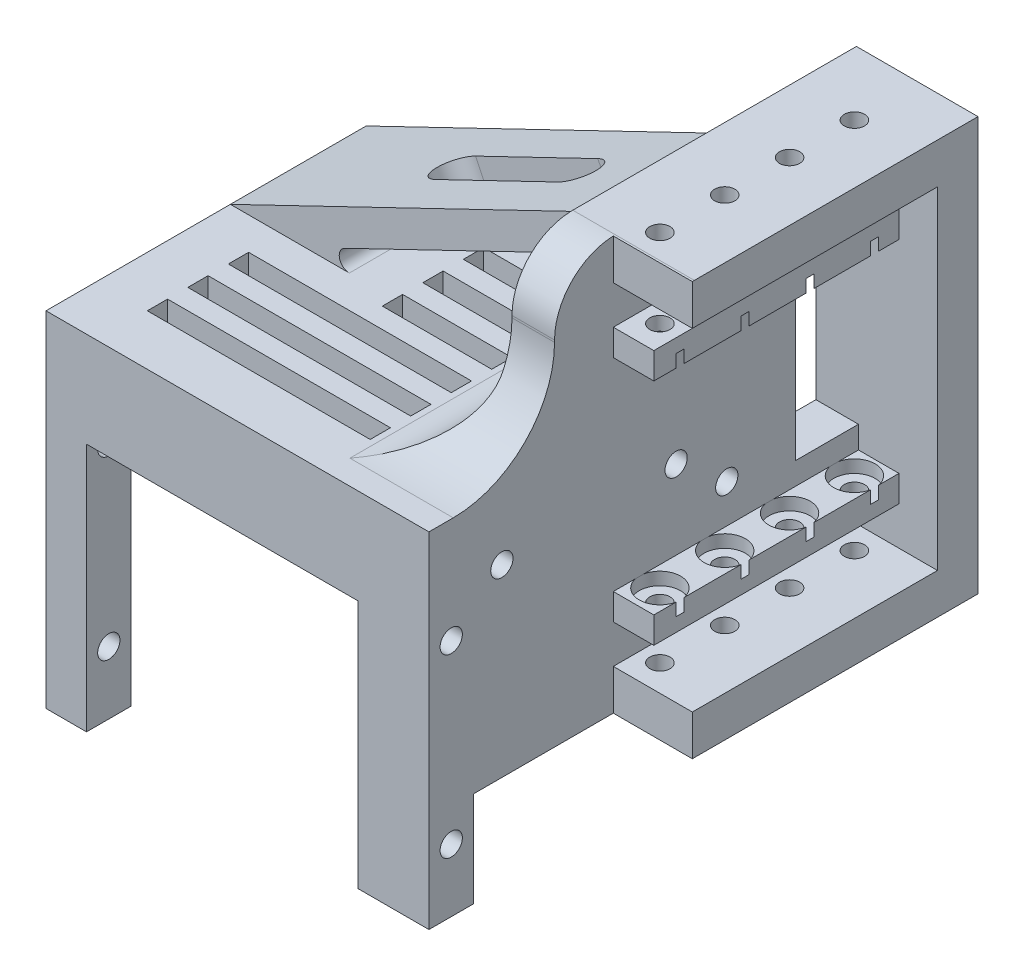
SolidWorks part; units mm, degrees
ref_plane "Front Plane" through (0, 0, 0) normal (0, 0, 1) x (1, 0, 0)
ref_plane "Top Plane" through (0, 0, 0) normal (0, 1, 0) x (1, 0, 0)
ref_plane "Right Plane" through (0, 0, 0) normal (1, 0, 0) x (0, 0, -1)
sketch "Sketch1" plane through (0, 0, 0) normal (0, 0, 1) x (1, 0, 0)
  line L1 (0, 0) -> (57.912, 0)
  line L2 (0, 0) -> (0, 63.754)
  line L3 (0, 63.754) -> (57.912, 63.754)
  line L4 (57.912, 0) -> (57.912, 63.754)
  dimension "D1" = 57.912
  dimension "D2" = 63.754
extrude "Boss-Extrude1" add sketch "Sketch1" against normal blind 58.928
sketch "Sketch3" plane through (0, 0, 0) normal (0, 0, 1) x (1, 0, 0)
  line L0 (42.672, 63.754) -> (0, 43.18)
  line L1 (42.672, 59.2423) -> (14.3644, 45.594)
  line L2 (14.9159, 43.18) -> (42.672, 43.18)
  line L3 (44.437, 60.0933) -> (1.765, 39.5193) construction
  line L4 (0, 63.754) -> (0, 0)
  line L5 (0, 0) -> (57.912, 0)
  line L6 (57.912, 0) -> (57.912, 63.754)
  line L7 (57.912, 63.754) -> (0, 63.754)
  line L8 (0, 63.754) -> (0, 43.18)
  line L9 (5.08, 0) -> (5.08, 31.242)
  line L10 (0, 0) -> (57.912, 0) construction
  line L11 (42.672, 63.754) -> (0, 63.754)
  line L12 (42.672, 59.2423) -> (42.672, 43.18)
  line L13 (5.08, 31.242) -> (39.116, 31.242)
  line L14 (39.116, 31.242) -> (39.116, 0)
  line L15 (5.08, 0) -> (39.116, 0)
  line L16 (48.006, 0) -> (48.006, 11.938)
  line L17 (48.006, 11.938) -> (57.912, 11.938)
  line L18 (57.912, 0) -> (57.912, 63.754) construction
  line L19 (57.912, 11.938) -> (57.912, 0)
  line L20 (48.006, 0) -> (57.912, 0)
  arc A0 (14.3644, 45.594) -> (14.9159, 43.18) centre (14.9159, 44.45) ccw
  dimension "D5" = 1.27
  dimension "D2" = 15.24
  dimension "D3" = 20.574
  dimension "D7" = 5.08
  dimension "D8" = 31.242
  dimension "D9" = 34.036
  dimension "D10" = 9.906
  dimension "D11" = 11.938
  dimension "D1" = 0
  dimension "D4" = 4.064
extrude "Cut-Extrude1" cut sketch "Sketch3" against normal through all
sketch "Sketch4" plane through (0, 63.754, 0) normal (0, 1, 0) x (1, 0, 0)
  line L0 (0, 0) -> (0, 18.796)
  line L1 (0, 58.928) -> (0, 0) construction
  line L2 (0, 18.796) -> (42.672, 18.796)
  line L3 (42.672, 58.928) -> (42.672, 0) construction
  line L4 (42.672, 18.796) -> (42.672, 0)
  line L5 (42.672, 0) -> (0, 0)
  line L6 (57.912, 35.814) -> (48.006, 35.814)
  line L7 (57.912, 58.928) -> (57.912, 0) construction
  line L8 (48.006, 35.814) -> (48.006, 58.928)
  line L9 (48.006, 58.928) -> (57.912, 58.928)
  line L10 (57.912, 58.928) -> (57.912, 35.814)
  line L11 (50.546, 35.814) -> (50.546, 32.512) construction
  circle A0 centre (50.546, 32.512) radius 1.27
  circle A1 centre (50.546, 24.384) radius 1.27
  circle A2 centre (50.546, 16.256) radius 1.27
  circle A3 centre (50.546, 8.128) radius 1.27
  dimension "D5" = 2.54
  dimension "D1" = 18.796
  dimension "D2" = 9.906
  dimension "D3" = 7.366
  dimension "D4" = 3.302
  dimension "D8" = 35.814
  dimension "D6" = 4
extrude "Cut-Extrude2" cut sketch "Sketch4" against normal through all
fillet "Fillet1" radius 2.54 1 edges at (42.672, 21.59, -18.796)
sketch "Sketch6" plane through (0, 63.754, 0) normal (0, 1, 0) x (1, 0, 0)
  line L0 (42.672, 35.814) -> (0, 35.814)
  line L1 (0, 58.928) -> (0, 18.796) construction
  line L2 (0, 35.814) -> (0, 58.928)
  line L3 (0, 58.928) -> (48.006, 58.928)
  line L4 (48.006, 58.928) -> (48.006, 43.18)
  line L5 (48.006, 58.928) -> (48.006, 35.814) construction
  line L6 (48.006, 43.18) -> (42.672, 43.18)
  line L7 (42.672, 58.928) -> (42.672, 18.796) construction
  line L8 (42.672, 43.18) -> (42.672, 35.814)
  line L9 (48.006, 35.814) -> (57.912, 35.814) construction
  dimension "D1" = 15.748
extrude "Cut-Extrude3" cut sketch "Sketch6" against normal blind 20.574
fillet "Fillet2" radius 12.7 1 edges at (45.339, 43.18, -43.18)
fillet "Fillet3" radius 7.62 1 edges at (42.672, 43.18, -36.068)
fillet "Fillet4" radius 7.62 1 edges at (45.339, 63.754, -43.18)
sketch "Sketch7" plane through (-16.8922, 35.0356, 0) normal (-0.4343, 0.9008, 0) x (0.9008, 0.4343, 0)
  line L0 (57.4899, 18.796) -> (57.4899, 24.638) construction
  line L1 (18.753, 18.796) -> (66.1259, 18.796) construction
  line L2 (57.4899, 24.638) -> (66.1259, 24.638) construction
  line L4 (57.4899, 24.638) -> (40.4719, 24.638)
  line L5 (57.4899, 29.718) -> (40.4719, 29.718)
  line L6 (66.1259, 35.56) -> (66.1259, 18.796) construction
  arc A0 (40.4719, 29.718) -> (40.4719, 24.638) centre (40.4719, 27.178) ccw
  arc A1 (57.4899, 29.718) -> (57.4899, 24.638) centre (57.4899, 27.178) cw
  dimension "D1" = 8.636
  dimension "D2" = 5.842
  dimension "D4" = 17.018
  dimension "D3" = 5.08
extrude "Cut-Extrude4" cut sketch "Sketch7" along direction (-0.4343, 0.9008, 0) on the side against the normal up to next (4.064 mm away)
sketch "Sketch8" plane through (0, 43.18, 0) normal (0, 1, 0) x (1, 0, 0)
  line L0 (6.35, 52.578) -> (34.29, 52.578)
  line L1 (34.29, 52.578) -> (34.29, 50.038)
  line L2 (34.29, 50.038) -> (6.35, 50.038)
  line L3 (6.35, 50.038) -> (6.35, 52.578)
  line L4 (0, 58.928) -> (0, 35.814) construction
  line L5 (0, 58.928) -> (48.006, 58.928) construction
  line L6 (34.29, 44.958) -> (6.35, 44.958)
  line L7 (34.29, 47.498) -> (34.29, 44.958)
  line L8 (6.35, 47.498) -> (34.29, 47.498)
  line L9 (6.35, 44.958) -> (6.35, 47.498)
  line L10 (34.29, 39.878) -> (6.35, 39.878)
  line L11 (34.29, 42.418) -> (34.29, 39.878)
  line L12 (6.35, 42.418) -> (34.29, 42.418)
  line L13 (6.35, 39.878) -> (6.35, 42.418)
  line L14 (34.29, 37.338) -> (20.574, 37.338)
  line L15 (34.29, 37.338) -> (34.29, 34.798)
  line L16 (34.29, 34.798) -> (20.574, 34.798)
  line L17 (20.574, 34.798) -> (20.574, 37.338)
  line L18 (34.29, 37.338) -> (6.35, 37.338) construction
  line L19 (34.29, 29.718) -> (20.574, 29.718)
  line L20 (34.29, 32.258) -> (34.29, 29.718)
  line L21 (34.29, 32.258) -> (20.574, 32.258)
  line L22 (20.574, 29.718) -> (20.574, 32.258)
  line L23 (34.29, 24.638) -> (20.574, 24.638)
  line L24 (34.29, 27.178) -> (34.29, 24.638)
  line L25 (34.29, 27.178) -> (20.574, 27.178)
  line L26 (20.574, 24.638) -> (20.574, 27.178)
  dimension "D1" = 6.35
  dimension "D2" = 6.35
  dimension "D3" = 2.54
  dimension "D4" = 27.94
  dimension "D7" = 2.54
  dimension "D8" = 13.716
  dimension "D6" = 2.54
  dimension "D5" = 3
  dimension "D9" = 3
extrude "Cut-Extrude5" cut sketch "Sketch8" against normal through all
sketch "Sketch9" plane through (0, 31.242, 0) normal (0, -1, 0) x (1, 0, 0)
  line L4 (39.116, -19.304) -> (5.08, -19.304)
  line L5 (5.08, -58.42) -> (39.116, -58.42)
  line L8 (39.116, -58.928) -> (39.116, -18.796)
  line L9 (39.116, -18.796) -> (5.08, -18.796)
  line L10 (5.08, -18.796) -> (5.08, -58.928)
  line L11 (5.08, -58.928) -> (39.116, -58.928)
  line L12 (39.116, -58.42) -> (39.116, -19.304)
  line L14 (5.08, -19.304) -> (5.08, -58.42)
  dimension "D1" = 0
extrude "Cut-Extrude6" cut sketch "Sketch9" against normal blind 5.588
sketch "Sketch10" plane through (5.08, 0, 0) normal (1, 0, 0) x (0, 0, -1)
  line L0 (58.42, 31.242) -> (54.6195, 36.83)
  line L1 (58.42, 36.83) -> (19.304, 36.83) construction
  line L2 (58.928, 31.242) -> (58.42, 31.242) construction
  line L3 (54.6195, 36.83) -> (58.42, 36.83)
  line L4 (58.42, 36.83) -> (58.42, 31.242)
  dimension "D1" = 124.22
extrude "Boss-Extrude3" add sketch "Sketch10" along direction (1, 0, 0) on the side of the normal up to next (34.036 mm away)
sketch "Sketch11" plane through (0, 31.242, 0) normal (0, -1, 0) x (1, 0, 0)
  line L0 (22.098, -58.928) -> (22.098, -18.796) construction
  line L1 (39.116, -58.928) -> (5.08, -58.928) construction
  line L2 (39.116, -18.796) -> (5.08, -18.796) construction
  line L3 (22.098, -38.862) -> (6.9192, -38.862) construction
ref_plane "Plane1" through (0, 0, -38.862) normal (0, 0, 1) x (1, 0, 0)
mirror "Mirror1" about plane through (0, 0, -38.862) normal (0, 0, 1) of "Boss-Extrude3"
fillet "Fillet5" radius 3.048 2 edges at (22.098, 36.83, -54.6195) (22.098, 36.83, -23.1045)
sketch "Sketch12" plane through (42.672, 0, 0) normal (-1, 0, 0) x (0, 0, 1)
  line L0 (0, 0) -> (0, 63.754) construction
  line L1 (-5.08, 27.94) -> (-12.954, 27.94)
  line L2 (-5.08, 27.94) -> (-5.08, 48.514)
  line L3 (-5.08, 48.514) -> (-12.954, 48.514)
  line L4 (-12.954, 27.94) -> (-12.954, 48.514)
  line L5 (0, 63.754) -> (-18.796, 63.754) construction
  line L6 (-53.34, 0) -> (-53.34, 11.938)
  line L7 (-58.928, 0) -> (-18.796, 0) construction
  line L8 (-53.34, 11.938) -> (-24.384, 11.938)
  line L9 (-24.384, 11.938) -> (-24.384, 2.5976)
  line L10 (-24.384, 2.5976) -> (-18.796, 2.5976)
  line L11 (-18.796, 0) -> (-18.796, 43.18) construction
  line L12 (-18.796, 2.5976) -> (-18.796, 11.938)
  line L13 (-18.796, 11.938) -> (0, 11.938)
  line L14 (0, 11.938) -> (0, 0)
  line L15 (0, 0) -> (-53.34, 0)
  line L16 (-58.928, 43.18) -> (-58.928, 0) construction
  dimension "D1" = 5.08
  dimension "D2" = 7.874
  dimension "D3" = 20.574
  dimension "D4" = 15.24
  dimension "D5" = 5.588
  dimension "D6" = 5.588
  dimension "D7" = 11.938
extrude "Cut-Extrude7" cut sketch "Sketch12" against normal through all both and the other way through all
sketch "Sketch14" plane through (0, 0, 0) normal (-1, 0, 0) x (0, 0, 1)
  line L0 (-53.34, 11.938) -> (-53.34, 32.258)
  line L1 (-53.34, 11.938) -> (-24.5287, 11.938)
  line L2 (-24.384, 11.938) -> (-53.34, 11.938) construction
  line L3 (-24.5287, 11.938) -> (-24.5287, 32.258)
  line L4 (-24.5287, 32.258) -> (-53.34, 32.258)
  dimension "D1" = 20.32
extrude "Cut-Extrude8" cut sketch "Sketch14" against normal up to surface (42.672 mm away) up to face at (42.672, 38.227, -9.017)
sketch "Sketch17" plane through (0, 0, 0) normal (-1, 0, 0) x (0, 0, 1)
  line L0 (-58.928, 0) -> (-53.34, 0) construction
  line L1 (-56.134, 0) -> (-56.134, 7.874) construction
  line L2 (-21.59, 2.5976) -> (-21.59, 0) construction
  line L3 (-18.796, 2.5976) -> (-24.384, 2.5976) construction
  line L4 (-38.862, 0) -> (-38.862, 39.1109) construction
  line L5 (-56.134, 0) -> (-21.59, 0) construction
  line L6 (-49.784, 32.258) -> (-49.784, 35.052) construction
  line L7 (-24.5287, 32.258) -> (-53.34, 32.258) construction
  circle A0 centre (-56.134, 7.874) radius 1.397
  circle A1 centre (-56.134, 29.972) radius 1.397
  circle A2 centre (-49.784, 35.052) radius 1.397
  circle A3 centre (-21.59, 7.874) radius 1.397
  circle A4 centre (-21.59, 29.972) radius 1.397
  circle A5 centre (-27.94, 35.052) radius 1.397
  dimension "D2" = 2.794
  dimension "D6" = 2.794
  dimension "D1" = 7.874
  dimension "D3" = 2
  dimension "D4" = 2.794
  dimension "D5" = 3.556
extrude "Cut-Extrude9" cut sketch "Sketch17" against normal through all
sketch "Sketch18" plane through (0, 0, -35.814) normal (0, 0, -1) x (-1, 0, 0)
  line L0 (-57.912, 58.6698) -> (-48.006, 58.6698)
  line L1 (-57.912, 11.938) -> (-57.912, 63.7498) construction
  line L2 (-48.006, 58.6698) -> (-48.006, 53.8438)
  line L3 (-48.006, 53.8438) -> (-53.086, 53.8438)
  line L4 (-53.086, 53.8438) -> (-53.086, 50.5418)
  line L5 (-53.086, 50.5418) -> (-48.006, 50.5418)
  line L6 (-48.006, 50.5418) -> (-48.006, 25.146)
  line L7 (-48.006, 37.8439) -> (-57.912, 37.8439) construction
  line L8 (-57.912, 17.018) -> (-57.912, 58.6698)
  line L9 (-57.912, 63.7519) -> (-57.912, 11.938) construction
  line L10 (-57.912, 63.754) -> (-57.912, 63.7498) construction
  line L11 (-48.006, 63.7498) -> (-57.912, 63.7498) construction
  line L12 (-57.912, 11.9359) -> (-57.912, 63.7498) construction
  line L13 (-53.086, 25.146) -> (-48.006, 25.146)
  line L14 (-53.086, 21.844) -> (-53.086, 25.146)
  line L15 (-48.006, 21.844) -> (-53.086, 21.844)
  line L16 (-48.006, 17.018) -> (-48.006, 21.844)
  line L17 (-57.912, 17.018) -> (-48.006, 17.018)
  point P15 (-57.912, 37.8449)
  dimension "D1" = 5.08
  dimension "D2" = 9.906
  dimension "D3" = 4.826
  dimension "D4" = 5.08
  dimension "D5" = 3.302
extrude "Cut-Extrude10" cut sketch "Sketch18" against normal blind 30.734
sketch "Sketch19" plane through (0, 25.146, 0) normal (0, 1, 0) x (1, 0, 0)
  circle A0 centre (50.546, 8.128) radius 1.27 construction
  circle A1 centre (50.546, 16.256) radius 1.27 construction
  circle A2 centre (50.546, 24.384) radius 1.27 construction
  circle A3 centre (50.546, 32.512) radius 1.27 construction
  circle A4 centre (50.546, 8.128) radius 1.27 construction
  circle A5 centre (50.546, 16.256) radius 1.27 construction
  circle A6 centre (50.546, 24.384) radius 1.27 construction
  circle A7 centre (50.546, 32.512) radius 1.27 construction
  circle A8 centre (50.546, 32.512) radius 2.5908
  circle A9 centre (50.546, 24.384) radius 2.5908
  circle A10 centre (50.546, 16.256) radius 2.5908
  circle A11 centre (50.546, 8.128) radius 2.5908
  dimension "D1" = 1.3208
  dimension "D2" = 1.3208
  dimension "D3" = 1.3208
  dimension "D4" = 1.3208
extrude "Cut-Extrude13" cut sketch "Sketch19" against normal blind 1.5875
sketch "Sketch20" plane through (0, 50.5418, 0) normal (0, -1, 0) x (1, 0, 0)
  circle A0 centre (50.546, -8.128) radius 1.27 construction
  circle A1 centre (50.546, -16.256) radius 1.27 construction
  circle A2 centre (50.546, -24.384) radius 1.27 construction
  circle A3 centre (50.546, -32.512) radius 1.27 construction
  circle A4 centre (50.546, -8.128) radius 1.27 construction
  circle A5 centre (50.546, -16.256) radius 1.27 construction
  circle A6 centre (50.546, -24.384) radius 1.27 construction
  circle A7 centre (50.546, -32.512) radius 1.27 construction
  circle A8 centre (50.546, -8.128) radius 2.5908
  circle A9 centre (50.546, -16.256) radius 2.5908
  circle A10 centre (50.546, -24.384) radius 2.5908
  circle A11 centre (50.546, -32.512) radius 2.5908
  dimension "D1" = 1.3208
  dimension "D2" = 1.3208
  dimension "D3" = 1.3208
  dimension "D4" = 1.3208
extrude "Cut-Extrude14" cut sketch "Sketch20" against normal blind 1.5875
mirror "Mirror2" about plane through (0, 0, 0) normal (0, 0, 1) of bodies 116
sketch "Sketch21" plane through (0, 63.754, 0) normal (0, 1, 0) x (1, 0, 0)
  line L0 (83.5536, 0) -> (-36.9665, 0)
  line L2 (-36.9665, 0) -> (-36.9665, 73.6411)
  line L3 (-36.9665, 73.6411) -> (83.5536, 73.6411)
  line L4 (83.5536, 73.6411) -> (83.5536, 0)
extrude "Cut-Extrude15" cut sketch "Sketch21" against normal through all
